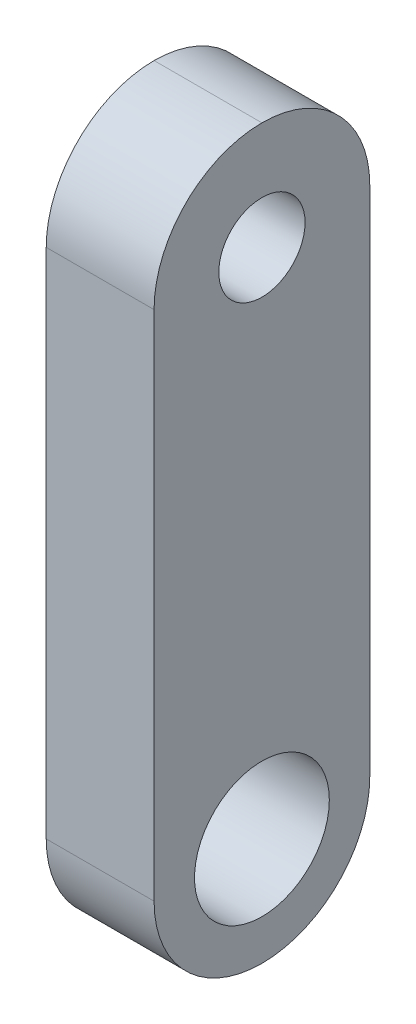
SolidWorks part; units mm, degrees
ref_plane "Front" through (0, 0, 0) normal (0, 0, 1) x (1, 0, 0)
ref_plane "Top" through (0, 0, 0) normal (0, 1, 0) x (1, 0, 0)
ref_plane "Right" through (0, 0, 0) normal (1, 0, 0) x (0, 0, -1)
sketch "Sketch1" plane through (0, 0, 0) normal (1, 0, 0) x (0, 0, -1)
  line L1 (0, 0) -> (8, 0)
  line L2 (0, 0) -> (0, -27)
  line L3 (0, -27) -> (8, -27)
  line L4 (8, 0) -> (8, -27)
  dimension "D1" = 27
  dimension "D2" = 8
extrude "Boss-Extrude1" add sketch "Sketch1" along normal blind 4
sketch "Sketch2" plane through (4, 0, 0) normal (1, 0, 0) x (0, 0, -1)
  line L0 (8, -27) -> (8, 0) construction
  line L1 (8, 0) -> (0, 0) construction
  line L2 (0, -27) -> (8, -27) construction
  circle A0 centre (4, -23) radius 2.5
  circle A1 centre (4, -4) radius 1.6
  dimension "D1" = 5
  dimension "D2" = 3.2
  dimension "D3" = 4
  dimension "D4" = 4
  dimension "D5" = 4
  dimension "D6" = 4
extrude "Cut-Extrude1" cut sketch "Sketch2" against normal through all
fillet "Fillet1" radius 4 4 edges at (2, -27, -8) (2, -27, 0) (2, 0, 0) (2, 0, -8)
